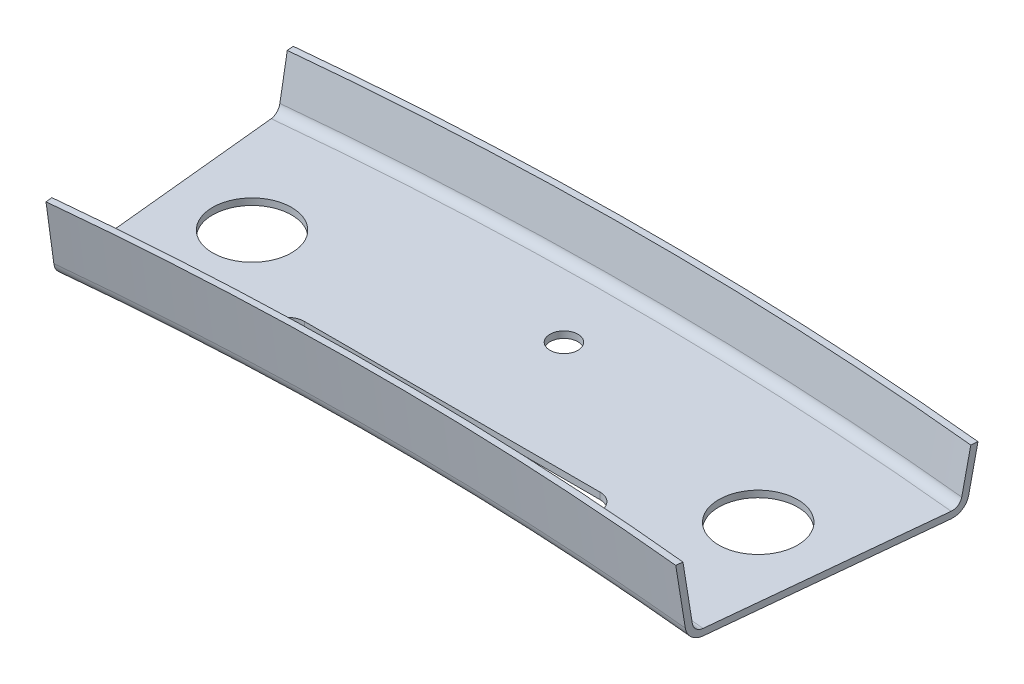
SolidWorks part; units mm, degrees
ref_plane "Front Plane" through (0, 0, 0) normal (0, 0, 1) x (1, 0, 0)
ref_plane "Top Plane" through (0, 0, 0) normal (0, 1, 0) x (1, 0, 0)
ref_plane "Right Plane" through (0, 0, 0) normal (1, 0, 0) x (0, 0, -1)
sketch "Sketch1" plane through (0, 0, 0) normal (0, 1, 0) x (1, 0, 0)
  arc A0 (-100, -5) -> (100, -5) centre (0, -1002.5) cw
  point P3 (0, 0)
  dimension "D1" = 5
  dimension "D2" = 200
sketch "Sketch2" plane through (0, 0, 0) normal (1, 0, 0) x (0, 0, -1)
  line L0 (-34.4785, 0) -> (34.4785, 0)
  line L2 (37.4203, 2.4117) -> (39.9379, 15)
  line L3 (39.9379, 15) -> (41.9379, 15)
  line L4 (41.9379, 15) -> (39.3418, 2.0194)
  line L5 (34.4389, -2) -> (-34.4561, -2)
  line L6 (-39.4008, 2.2583) -> (-42.0621, 20)
  line L7 (-42.0621, 20) -> (-40.0621, 20)
  line L9 (-40.0621, 20) -> (-37.4453, 2.555)
  arc A1 (-34.4785, 0) -> (-37.4453, 2.555) centre (-34.4785, 3) cw
  arc A2 (-34.4561, -2) -> (-39.4008, 2.2583) centre (-34.4561, 3) cw
  arc A3 (39.3418, 2.0194) -> (34.4389, -2) centre (34.4389, 3) cw
  arc A4 (37.4203, 2.4117) -> (34.4785, 0) centre (34.4785, 3) cw
  point P3 (-37.0621, 0)
  point P11 (0, 0)
  point P14 (36.9379, 0)
  point P23 (36.9379, 0)
  dimension "D6" = 3
  dimension "D8" = 3
  dimension "D9" = 5
  dimension "D10" = 5
  dimension "D11" = 3
  dimension "D1" = 17
  dimension "D2" = 80
  dimension "D3" = 3
  dimension "D4" = 2
  dimension "D5" = 2
  dimension "D7" = 22
sweep "Sweep1" add profiles "Sketch2" path "Sketch1"
sketch "Sketch3" plane through (0, 0, 0) normal (0, 1, 0) x (1, 0, 0)
  circle A0 centre (0, 14.9379) radius 4.25
  circle A2 centre (-77, -2.9615) radius 12
  circle A3 centre (77, -2.9615) radius 12
  arc A4 (-77, -2.9615) -> (77, -2.9615) centre (0, -1002.5) cw construction
  arc A5 (95.8043, -46.8523) -> (-95.8043, -46.8523) centre (0, -1002.5) ccw construction
  arc A6 (103.9838, 34.7387) -> (-103.9838, 34.7387) centre (0, -1002.5) ccw construction
  point P8 (0, 39.9379)
  point P12 (0, 0)
  dimension "D1" = 8.5
  dimension "D3" = 24
  dimension "D2" = 25
  dimension "D4" = 154
extrude "Mounting points" cut sketch "Sketch3" against normal through all both and the other way through all
sketch "Sketch4" plane through (0, 0, 0) normal (0, 1, 0) x (1, 0, 0)
  line L0 (-45, -24.0621) -> (45, -24.0621) construction
  line L1 (-45, -19.0621) -> (45, -19.0621)
  line L2 (-45, -29.0621) -> (45, -29.0621)
  arc A0 (-45, -19.0621) -> (-45, -29.0621) centre (-45, -24.0621) ccw
  arc A1 (45, -29.0621) -> (45, -19.0621) centre (45, -24.0621) ccw
  circle A3 centre (0, 14.9379) radius 4.25 construction
  point P2 (0, -24.0621)
  dimension "D1" = 5
  dimension "D2" = 90
  dimension "D3" = 34
extrude "Slot clearance" cut sketch "Sketch4" against normal through all both and the other way through all
